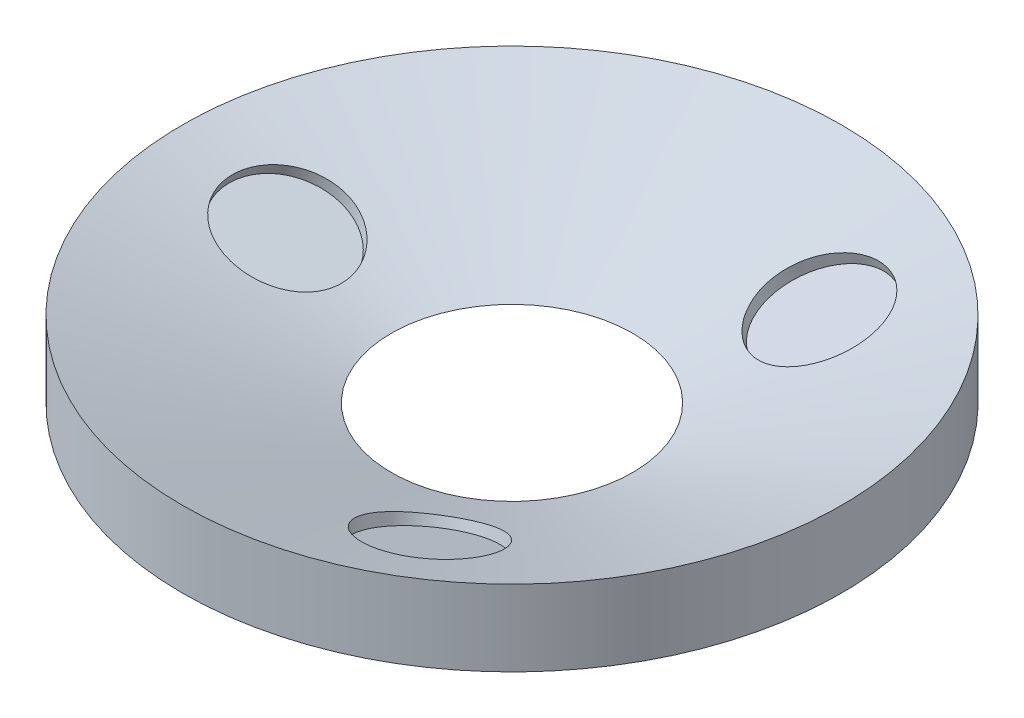
SolidWorks part; units mm, degrees
material "HDPE"
ref_plane "Piano frontale" through (0, 0, 0) normal (0, 0, 1) x (1, 0, 0)
ref_plane "Piano superiore" through (0, 0, 0) normal (0, 1, 0) x (1, 0, 0)
ref_plane "Piano destro" through (0, 0, 0) normal (1, 0, 0) x (0, 0, -1)
sketch "Schizzo1" plane through (0, 0, 0) normal (0, 0, 1) x (1, 0, 0)
  line L0 (-71, 16.3787) -> (-71, 0)
  line L1 (-71, 0) -> (-26, 0)
  line L2 (-26, 0) -> (-71, 16.3787)
  line L3 (0, 0) -> (0, 150.3289) construction
  dimension "D1" = 45
  dimension "D2" = 20
  dimension "D3" = 52
revolve "Rivoluzione1" add sketch "Schizzo1" angle 360 about L3
ref_plane "Piano1" through (-3.0414, -8.3562, 0) normal (0.342, 0.9397, 0) x (-0.9397, 0.342, 0)
sketch "Schizzo2" plane through (-3.0414, -8.3562, 0) normal (0.342, 0.9397, 0) x (-0.9397, 0.342, 0)
  line L0 (24.432, 0) -> (72.32, 0) construction
  circle A0 centre (48.376, 0) radius 12.5
  dimension "D1" = 25
extrude "Taglio-Estrusione5" cut sketch "Schizzo2" against normal blind 2 and the other way blind 10 contours A0
pattern_circular "RipetizioneCircolare1" count 3 every 120 about axis through (0, 16.3787, 0) along (0, -1, 0) of "Taglio-Estrusione5"
